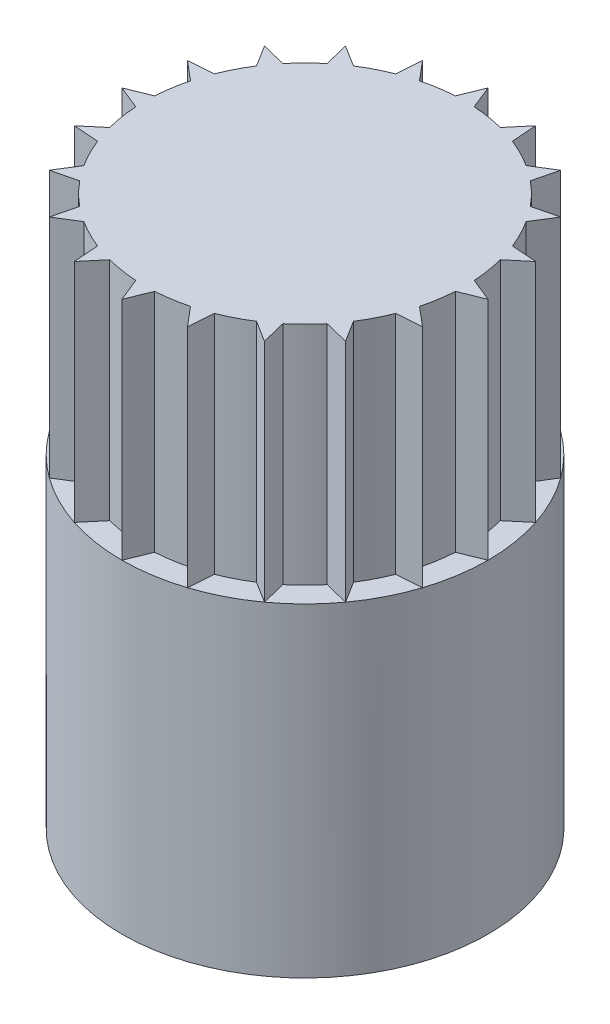
SolidWorks part; units mm, degrees
ref_plane "Front Plane" through (0, 0, 0) normal (0, 0, 1) x (1, 0, 0)
ref_plane "Top Plane" through (0, 0, 0) normal (0, 1, 0) x (1, 0, 0)
ref_plane "Right Plane" through (0, 0, 0) normal (1, 0, 0) x (0, 0, -1)
sketch "Sketch1" plane through (0, 0, 0) normal (0, 1, 0) x (1, 0, 0)
  circle A0 centre (0, 0) radius 4.86
  dimension "D1" = 9.72
extrude "Boss-Extrude1" add sketch "Sketch1" along normal blind 8.6
sketch "Sketch2" plane through (0, 8.6, 0) normal (0, 1, 0) x (1, 0, 0)
  line L0 (0, 4.86) -> (0.2508, 4.2426)
  line L2 (0, 4.86) -> (-0.2508, 4.2426)
  line L3 (1.5018, 4.6221) -> (1.5495, 3.9575)
  line L4 (1.5018, 4.6221) -> (1.0726, 4.1124)
  line L5 (2.8566, 3.9318) -> (2.6966, 3.2849)
  line L6 (2.8566, 3.9318) -> (2.2909, 3.5797)
  line L7 (3.9318, 2.8566) -> (3.5797, 2.2909)
  line L8 (3.9318, 2.8566) -> (3.2849, 2.6966)
  line L9 (4.6221, 1.5018) -> (4.1124, 1.0726)
  line L10 (4.6221, 1.5018) -> (3.9575, 1.5495)
  line L11 (4.86, 0) -> (4.2426, -0.2508)
  line L12 (4.86, 0) -> (4.2426, 0.2508)
  line L13 (4.6221, -1.5018) -> (3.9575, -1.5495)
  line L14 (4.6221, -1.5018) -> (4.1124, -1.0726)
  line L15 (3.9318, -2.8566) -> (3.2849, -2.6966)
  line L16 (3.9318, -2.8566) -> (3.5797, -2.2909)
  line L17 (2.8566, -3.9318) -> (2.2909, -3.5797)
  line L18 (2.8566, -3.9318) -> (2.6966, -3.2849)
  line L19 (1.5018, -4.6221) -> (1.0726, -4.1124)
  line L20 (1.5018, -4.6221) -> (1.5495, -3.9575)
  line L21 (0, -4.86) -> (-0.2508, -4.2426)
  line L22 (0, -4.86) -> (0.2508, -4.2426)
  line L23 (-1.5018, -4.6221) -> (-1.5495, -3.9575)
  line L24 (-1.5018, -4.6221) -> (-1.0726, -4.1124)
  line L25 (-2.8566, -3.9318) -> (-2.6966, -3.2849)
  line L26 (-2.8566, -3.9318) -> (-2.2909, -3.5797)
  line L27 (-3.9318, -2.8566) -> (-3.5797, -2.2909)
  line L28 (-3.9318, -2.8566) -> (-3.2849, -2.6966)
  line L29 (-4.6221, -1.5018) -> (-4.1124, -1.0726)
  line L30 (-4.6221, -1.5018) -> (-3.9575, -1.5495)
  line L31 (-4.86, 0) -> (-4.2426, 0.2508)
  line L32 (-4.86, 0) -> (-4.2426, -0.2508)
  line L33 (-4.6221, 1.5018) -> (-3.9575, 1.5495)
  line L34 (-4.6221, 1.5018) -> (-4.1124, 1.0726)
  line L35 (-3.9318, 2.8566) -> (-3.2849, 2.6966)
  line L36 (-3.9318, 2.8566) -> (-3.5797, 2.2909)
  line L37 (-2.8566, 3.9318) -> (-2.2909, 3.5797)
  line L38 (-2.8566, 3.9318) -> (-2.6966, 3.2849)
  line L39 (-1.5018, 4.6221) -> (-1.0726, 4.1124)
  line L40 (-1.5018, 4.6221) -> (-1.5495, 3.9575)
  arc A0 (-1.5495, 3.9575) -> (-2.2909, 3.5797) centre (0, 0) ccw
  circle A1 centre (0, 0) radius 4.86 construction
  arc A2 (-0.2508, 4.2426) -> (-1.0726, 4.1124) centre (0, 0) ccw
  arc A3 (1.0726, 4.1124) -> (0.2508, 4.2426) centre (0, 0) ccw
  arc A4 (2.2909, 3.5797) -> (1.5495, 3.9575) centre (0, 0) ccw
  arc A5 (3.2849, 2.6966) -> (2.6966, 3.2849) centre (0, 0) ccw
  arc A6 (3.9575, 1.5495) -> (3.5797, 2.2909) centre (0, 0) ccw
  arc A7 (4.2426, 0.2508) -> (4.1124, 1.0726) centre (0, 0) ccw
  arc A8 (4.1124, -1.0726) -> (4.2426, -0.2508) centre (0, 0) ccw
  arc A9 (3.5797, -2.2909) -> (3.9575, -1.5495) centre (0, 0) ccw
  arc A10 (2.6966, -3.2849) -> (3.2849, -2.6966) centre (0, 0) ccw
  arc A11 (1.5495, -3.9575) -> (2.2909, -3.5797) centre (0, 0) ccw
  arc A12 (0.2508, -4.2426) -> (1.0726, -4.1124) centre (0, 0) ccw
  arc A13 (-1.0726, -4.1124) -> (-0.2508, -4.2426) centre (0, 0) ccw
  arc A14 (-2.2909, -3.5797) -> (-1.5495, -3.9575) centre (0, 0) ccw
  arc A15 (-3.2849, -2.6966) -> (-2.6966, -3.2849) centre (0, 0) ccw
  arc A16 (-3.9575, -1.5495) -> (-3.5797, -2.2909) centre (0, 0) ccw
  arc A17 (-4.2426, -0.2508) -> (-4.1124, -1.0726) centre (0, 0) ccw
  arc A18 (-4.1124, 1.0726) -> (-4.2426, 0.2508) centre (0, 0) ccw
  arc A19 (-3.5797, 2.2909) -> (-3.9575, 1.5495) centre (0, 0) ccw
  arc A20 (-2.6966, 3.2849) -> (-3.2849, 2.6966) centre (0, 0) ccw
  point P7 (0.1254, 4.5513)
  point P69 (0, 0)
  dimension "D1" = 8.5
  dimension "D2" = 20
extrude "Boss-Extrude2" add sketch "Sketch2" along normal blind 6
